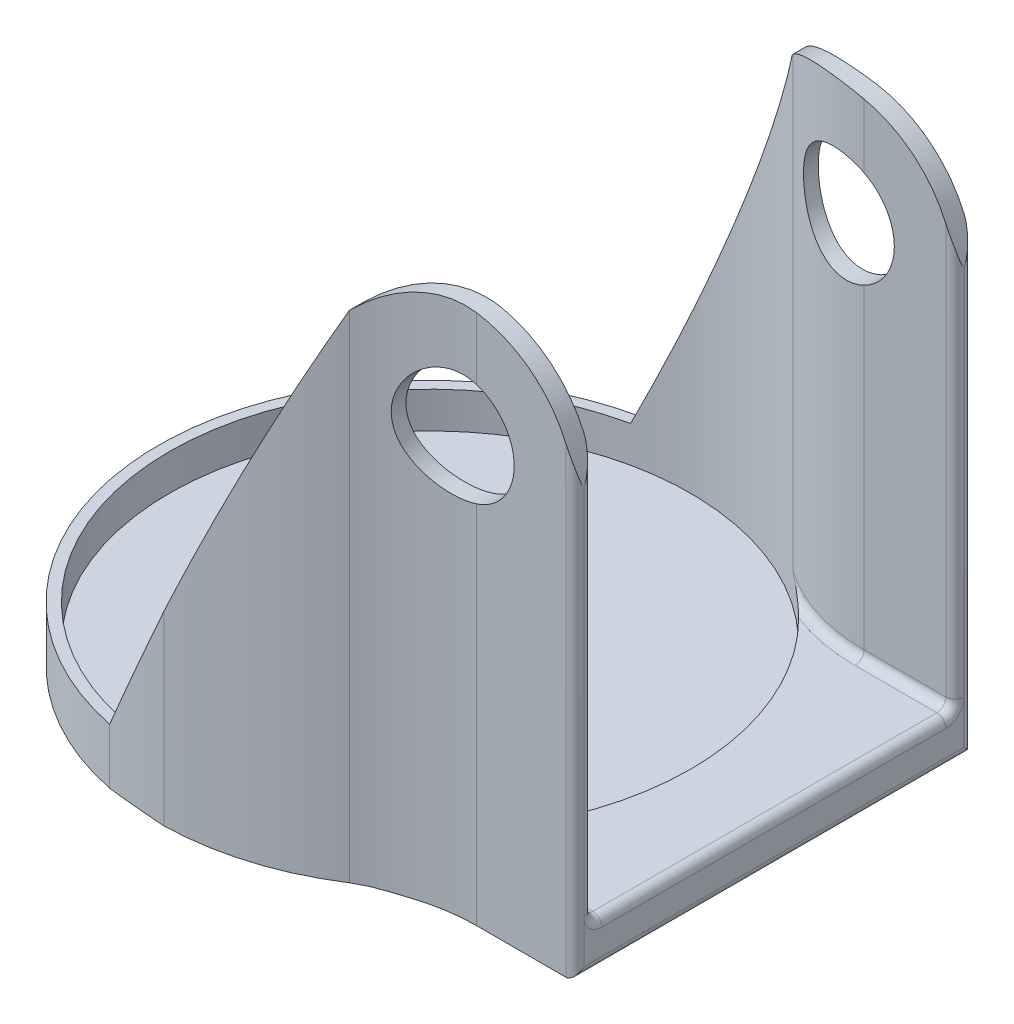
SolidWorks part; units mm, degrees
ref_plane "Plano frontal" through (0, 0, 0) normal (0, 0, 1) x (1, 0, 0)
ref_plane "Plano superior" through (0, 0, 0) normal (0, 1, 0) x (1, 0, 0)
ref_plane "Plano direito" through (0, 0, 0) normal (1, 0, 0) x (0, 0, -1)
sketch "Esboço1" plane through (0, 0, 0) normal (0, 1, 0) x (1, 0, 0)
  circle A0 centre (0, 0) radius 15
  dimension "D1" = 30
extrude "Ressalto-extrusão1" add sketch "Esboço1" along normal blind 1.2
sketch "Esboço2" plane through (0, 1.2, 0) normal (0, 1, 0) x (1, 0, 0)
  line L1 (-3, 15) -> (19, 15)
  line L2 (-3, 15) -> (-3, -15)
  line L3 (-3, -15) -> (19, -15)
  line L4 (19, 15) -> (19, -15)
  dimension "D1" = 22
  dimension "D2" = 3
  dimension "D3" = 15
  dimension "D4" = 15
extrude "Ressalto-extrusão2" add sketch "Esboço2" along normal blind 1.2 and the other way blind 1.2
sketch "Esboço3" plane through (0, 1.2, 0) normal (0, 1, 0) x (1, 0, 0)
  circle A0 centre (0, 0) radius 14.4
  dimension "D1" = 28.8
extrude "Corte-extrusão2" cut sketch "Esboço3" along normal blind 1.2
sketch "Esboço5" plane through (0, 1.2, 0) normal (0, 1, 0) x (1, 0, 0)
  line L0 (19, 15) -> (-3, 15) construction
  line L1 (0.3889, 15) -> (-3, 15)
  line L2 (-3, 15) -> (-3, 14.6969)
  line L3 (0, 0) -> (-7.8402, 0) construction
  line L4 (-3, -15) -> (-3, -14.6969)
  line L5 (0.3889, -15) -> (-3, -15)
  arc A0 (-3, 14.6969) -> (0.3889, 15) centre (1.3623, -14.9842) cw
  arc A1 (-3, -14.6969) -> (0.3889, -15) centre (1.3623, 14.9842) ccw
  dimension "D1" = 30
extrude "Corte-extrusão3" cut sketch "Esboço5" against normal through all and the other way through all
sketch "Esboço6" plane through (0, 2.4, 0) normal (0, 1, 0) x (1, 0, 0)
  line L0 (19, 11) -> (13.5647, 11)
  line L1 (19, -15) -> (19, 15) construction
  line L2 (19, 11) -> (19, 15)
  line L3 (19, 15) -> (0, 15)
  line L4 (0, 0) -> (19, 0) construction
  line L5 (19, -15) -> (0, -15)
  line L6 (19, -11) -> (19, -15)
  line L7 (19, -11) -> (13.5647, -11)
  arc A0 (8.1388, 12.6) -> (0, 15) centre (0, 0) ccw
  arc A1 (8.1388, -12.6) -> (0, -15) centre (0, 0) cw
  arc A2 (8.1388, -12.6) -> (13.5647, -11) centre (13.5647, -21) cw
  arc A3 (13.5647, 11) -> (8.1388, 12.6) centre (13.5647, 21) cw
  point P17 (10.198, -11)
  point P20 (10.198, 11)
  dimension "D2" = 10
  dimension "D1" = 11
extrude "Corte-extrusão4" cut sketch "Esboço6" against normal through all
sketch "Esboço7" plane through (0, 1.2, 0) normal (0, 1, 0) x (1, 0, 0)
  line L0 (-3, 14.6969) -> (-3, 14.084)
  line L1 (-3, -14.084) -> (-3, -14.6969)
  line L2 (-3, -14.6969) -> (-2.9829, -14.6922)
  arc A0 (-3, 14.6969) -> (-3, -14.6969) centre (0, 0) ccw construction
  arc A1 (-3, 14.6969) -> (-3, -14.6969) centre (0, 0) ccw
  arc A2 (-3, 14.084) -> (-3, -14.084) centre (0, 0) ccw
  line M2 (-3, 14.084) -> (-3, 14.6969)
  arc M3 (-3, 14.6969) -> (-3, -14.6969) centre (0, 0) ccw
  line M4 (-3, -14.6969) -> (-3, -14.084)
sketch "Esboço8" plane through (0, 2.4, 0) normal (0, 1, 0) x (1, 0, 0)
  line L5 (19, 11) -> (13.5647, 11)
  line L6 (-3, 14.6969) -> (-3, 14.084)
  line L7 (-3, -14.084) -> (-3, -14.6969)
  line L8 (13.5647, -11) -> (19, -11)
  line L9 (19, -11) -> (19, 11)
  line L10 (19, 11) -> (13.5647, 11)
  line L11 (-3, 14.6969) -> (-3, 14.084)
  line L12 (-3, -14.084) -> (-3, -14.6969)
  line L13 (13.5647, -11) -> (19, -11)
  line L14 (19, -11) -> (19, 11)
  arc A7 (8.1388, 12.6) -> (13.5647, 11) centre (13.5647, 21) ccw
  arc A8 (8.1388, 12.6) -> (0.3003, 14.997) centre (0, 0) ccw
  arc A9 (0.3003, 14.997) -> (-3, 14.6969) centre (1.3623, -14.9842) ccw
  arc A10 (-3, -14.084) -> (-3, 14.084) centre (0, 0) ccw
  arc A11 (-3, -14.6969) -> (0.3003, -14.997) centre (1.3623, 14.9842) ccw
  arc A12 (0.3003, -14.997) -> (8.1388, -12.6) centre (0, 0) ccw
  arc A13 (13.5647, -11) -> (8.1388, -12.6) centre (13.5647, -21) ccw
  arc A14 (8.1388, 12.6) -> (13.5647, 11) centre (13.5647, 21) ccw
  arc A15 (8.1388, 12.6) -> (0.3003, 14.997) centre (0, 0) ccw
  arc A16 (0.3003, 14.997) -> (-3, 14.6969) centre (1.3623, -14.9842) ccw
  arc A17 (-3, -14.084) -> (-3, 14.084) centre (0, 0) ccw
  arc A18 (-3, -14.6969) -> (0.3003, -14.997) centre (1.3623, 14.9842) ccw
  arc A19 (0.3003, -14.997) -> (8.1388, -12.6) centre (0, 0) ccw
  arc A20 (13.5647, -11) -> (8.1388, -12.6) centre (13.5647, -21) ccw
  dimension "D1" = 0
extrude "Ressalto-extrusão4" add sketch "Esboço8" along normal blind 27
extrude "Ressalto-extrusão5" add sketch "Esboço7" along normal blind 2 contours A2 M2 M3 M4 region at (-3.3175, 1.2, -14.3905)
sketch "Esboço10" plane through (0, 0, 0) normal (0, 0, 1) x (1, 0, 0)
  line L0 (-3, 3.2) -> (9, 29.4)
  line L1 (13.5647, 29.4) -> (8.1388, 29.4) construction
  line L2 (9, 29.4) -> (-3, 29.4)
  line L3 (-3, 29.4) -> (-3, 3.2)
  line L4 (19, 0) -> (19, 29.4) construction
  dimension "D1" = 10
extrude "Corte-extrusão5" cut sketch "Esboço10" against normal through all and the other way through all
sketch "Esboço11" plane through (0, 29.4, 0) normal (0, 1, 0) x (1, 0, 0)
  line L0 (19, -11) -> (19, 11) construction
  line L1 (9.8, -10) -> (19, -10)
  line L2 (9.8, -10) -> (9.8, 10)
  line L3 (9.8, 10) -> (19, 10)
  line L4 (19, -10) -> (19, 10)
  line L5 (9.8, -10) -> (19, 10) construction
  line L6 (9.8, 10) -> (19, -10) construction
  line L7 (19, 11) -> (13.5647, 11) construction
  arc A0 (9, -11.241) -> (9, 11.241) centre (0, 0) ccw construction
  point P0 (14.4, 0)
  dimension "D1" = 1
extrude "Corte-extrusão6" cut sketch "Esboço11" against normal blind 27
fillet "Filete1" radius 10 2 edges at (10.3615, 15.9, 10) (10.3615, 15.9, -10)
sketch "Esboço12" plane through (0, 0, 0) normal (0, 0, 1) x (1, 0, 0)
  line L0 (19, 0) -> (19, 29.4) construction
  line L1 (8.1388, 27.5197) -> (8.1388, 30.6814)
  line L2 (8.1388, 30.6814) -> (19.019, 30.6814)
  line L3 (19.019, 30.6814) -> (19, 23.4841)
  arc A0 (8.1388, 27.5197) -> (19, 23.4841) centre (12.6521, 23.0331) cw
extrude "Corte-extrusão7" cut sketch "Esboço12" against normal blind 27 and the other way blind 27
sketch "Esboço13" plane through (0, 0, 0) normal (0, 0, 1) x (1, 0, 0)
  circle A0 centre (12.6521, 23.0331) radius 3
  dimension "D1" = 6
extrude "Corte-extrusão8" cut sketch "Esboço13" against normal blind 27 and the other way blind 27
sketch "Esboço14" plane through (0, 0, 0) normal (0, -1, 0) x (1, 0, 0)
  circle A0 centre (0, 0) radius 14.5
  circle A1 centre (0, 0) radius 12.5
  dimension "D1" = 29
  dimension "D2" = 2
extrude "Corte-extrusão10" cut sketch "Esboço14" against normal blind 1
fillet "Filete4" radius 1 2 edges at (0, 0, -14.5) (0, 0, -12.5)
sketch "Esboço15" plane through (0, 0, 0) normal (0, -1, 0) x (1, 0, 0)
  circle A0 centre (0, 0) radius 3
  dimension "D1" = 6
extrude "Corte-extrusão11" cut sketch "Esboço15" against normal up to next
sketch "Esboço16" plane through (0, 0, 0) normal (0, -1, 0) x (1, 0, 0)
  circle A0 centre (0, 0) radius 11
  circle A1 centre (0, 0) radius 9
  dimension "D1" = 22
  dimension "D2" = 2
extrude "Corte-extrusão12" cut sketch "Esboço16" against normal blind 1
fillet "Filete6" radius 1 2 edges at (0, 0, -9) (0, 0, -11)
fillet "Filete8" radius 0.5 4 edges at (10.9744, 2.4, -10.4615) (10.9744, 2.4, 10.4615) (16.4886, 2.4, -10) (16.4886, 2.4, 10)
fillet "Filete9" radius 0.5 8 edges at (19, 11.7421, -11) (19, 11.7421, 11) (19, 0, 0) (19, 13.1921, 10) (19, 2.5464, 9.8536) (19, 13.1921, -10) (19, 2.5464, -9.8536) (19, 2.4, 0)
